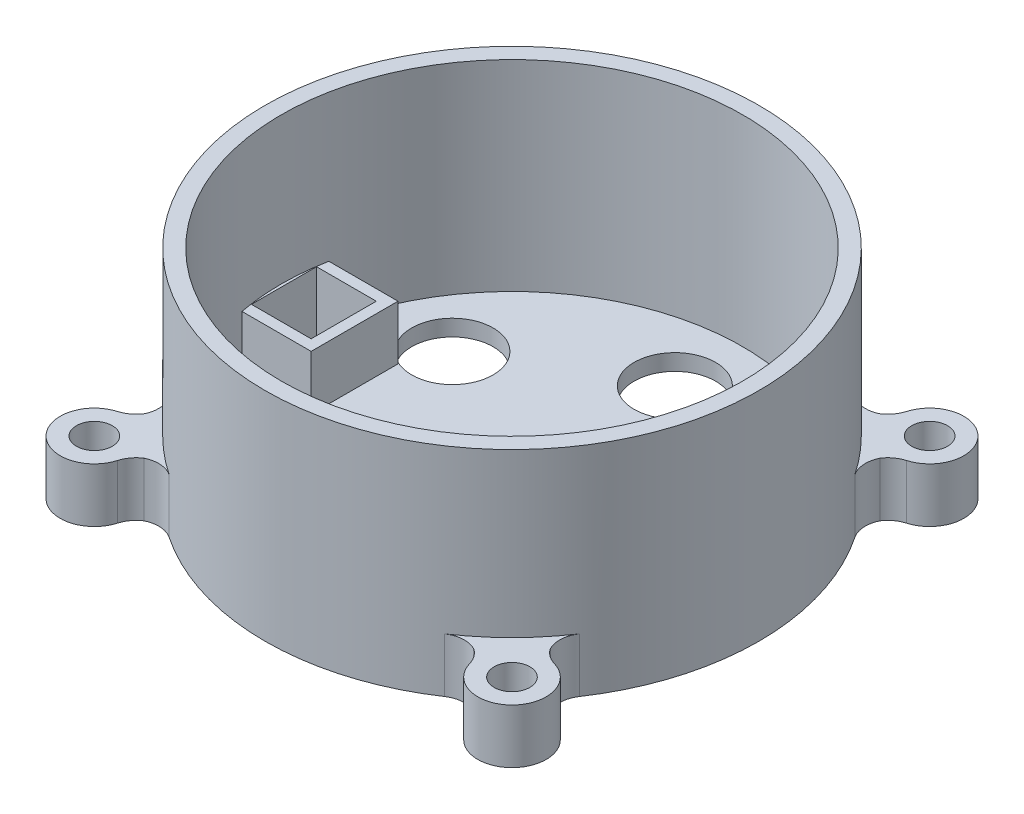
SolidWorks part; units mm, degrees
ref_plane "Front Plane" through (0, 0, 0) normal (0, 0, 1) x (1, 0, 0)
ref_plane "Top Plane" through (0, 0, 0) normal (0, 1, 0) x (1, 0, 0)
ref_plane "Right Plane" through (0, 0, 0) normal (1, 0, 0) x (0, 0, -1)
sketch "Sketch1" plane through (0, 0, 0) normal (0, 1, 0) x (1, 0, 0)
  circle A0 centre (0, 0) radius 45.5
  dimension "D1" = 91
extrude "Boss-Extrude1" add sketch "Sketch1" along normal blind 40
shell "Shell1" thickness 3 removed face at (0, 40, 45.5)
sketch "Sketch3" plane through (0, 0, 0) normal (0, -1, 0) x (1, 0, 0)
  line L0 (-78.2757, 0) -> (93.912, 0) construction
  line L1 (0, -51.8142) -> (0, 50.9292) construction
  circle A2 centre (0, 30) radius 7.5
  circle A3 centre (25.9808, 15) radius 7.5
  circle A4 centre (25.9808, -15) radius 7.5
  circle A5 centre (0, -30) radius 7.5
  circle A6 centre (-25.9808, -15) radius 7.5
  circle A7 centre (-25.9808, 15) radius 7.5
  point P5 (0, 0)
  point P24 (0, 0)
  dimension "D5" = 15
  dimension "D6" = 30
  dimension "D8" = 30
  dimension "D7" = 6
extrude "Cut-Extrude2" cut sketch "Sketch3" against normal through all both and the other way through all
sketch "Sketch4" plane through (0, 3, 0) normal (0, 1, 0) x (1, 0, 0)
  circle A0 centre (0, 0) radius 3
  dimension "D1" = 6
extrude "Cut-Extrude3" cut sketch "Sketch4" against normal up to surface (3 mm away) up to face at (25.9808, 0, 22.5)
sketch "Sketch6" plane through (0, 3, 0) normal (0, 1, 0) x (1, 0, 0)
  line L0 (0, 0) -> (-13.2822, 0) construction
  line L1 (-42, 6) -> (-31, 6)
  line L2 (-42, 6) -> (-42, -6)
  line L3 (-42, -6) -> (-31, -6)
  line L4 (-31, 6) -> (-31, -6)
  line L6 (-44, -8) -> (-29, -8)
  line L7 (-44, -8) -> (-44, 8)
  line L8 (-44, 8) -> (-29, 8)
  line L9 (-29, -8) -> (-29, 8)
  point P7 (-31, 0)
  dimension "D1" = 11
  dimension "D2" = 12
  dimension "D3" = 31
  dimension "D4" = 2
  dimension "D5" = 2
  dimension "D6" = 2
  dimension "D7" = 2
extrude "Boss-Extrude2" add sketch "Sketch6" along normal blind 10
sketch "Sketch7" plane through (0, 3, 0) normal (0, 1, 0) x (1, 0, 0)
  line L7 (-42, 6) -> (-31, 6)
  line L8 (-42, 6) -> (-42, -6)
  line L9 (-42, -6) -> (-31, -6)
  line L10 (-31, 6) -> (-31, -6)
extrude "Cut-Extrude5" cut sketch "Sketch7" against normal up to surface (3 mm away) up to face at (0, 0, 3)
sketch "Sketch8" plane through (0, 0, 0) normal (0, 1, 0) x (1, 0, 0)
  line L0 (0, 53.7357) -> (0, -59.836) construction
  line L1 (-43.8183, -43.8183) -> (52.9082, 52.9082) construction
  line L2 (32.1666, 38.4666) -> (27.8548, 35.9772)
  line L3 (38.4666, 32.1666) -> (35.9772, 27.8548)
  circle A0 centre (38.4666, 38.4666) radius 3.3
  arc A4 (38.4666, 32.1666) -> (32.1666, 38.4666) centre (38.4666, 38.4666) ccw
  circle A5 centre (0, 0) radius 45.5 construction
  arc A6 (27.8548, 35.9772) -> (35.9772, 27.8548) centre (0, 0) cw
  point P13 (38.4666, 32.1666)
  point P14 (0, 0)
  point P15 (0, 0)
  dimension "D2" = 6.6
  dimension "D3" = 12.6
  dimension "D5" = 15
  dimension "D1" = 45
  dimension "D4" = 54.4
  dimension "D6" = 15
extrude "Boss-Extrude3" add sketch "Sketch8" along normal blind 10
pattern_circular "CirPattern1" count 4 over 360 about axis through (0, 3, 0) along (0, 1, 0) of "Boss-Extrude3"
fillet "Fillet1" radius 5 16 edges at (-38.4666, 5, 32.1666) (-32.1666, 5, 38.4666) (-27.8548, 5, 35.9772) (-35.9772, 5, 27.8548) (32.1666, 5, 38.4666) (27.8548, 5, 35.9772) (38.4666, 5, 32.1666) (35.9772, 5, 27.8548) (38.4666, 5, -32.1666) (35.9772, 5, -27.8548) (32.1666, 5, -38.4666) (27.8548, 5, -35.9772) (-27.8548, 5, -35.9772) (-32.1666, 5, -38.4666) (-35.9772, 5, -27.8548) (-38.4666, 5, -32.1666)
